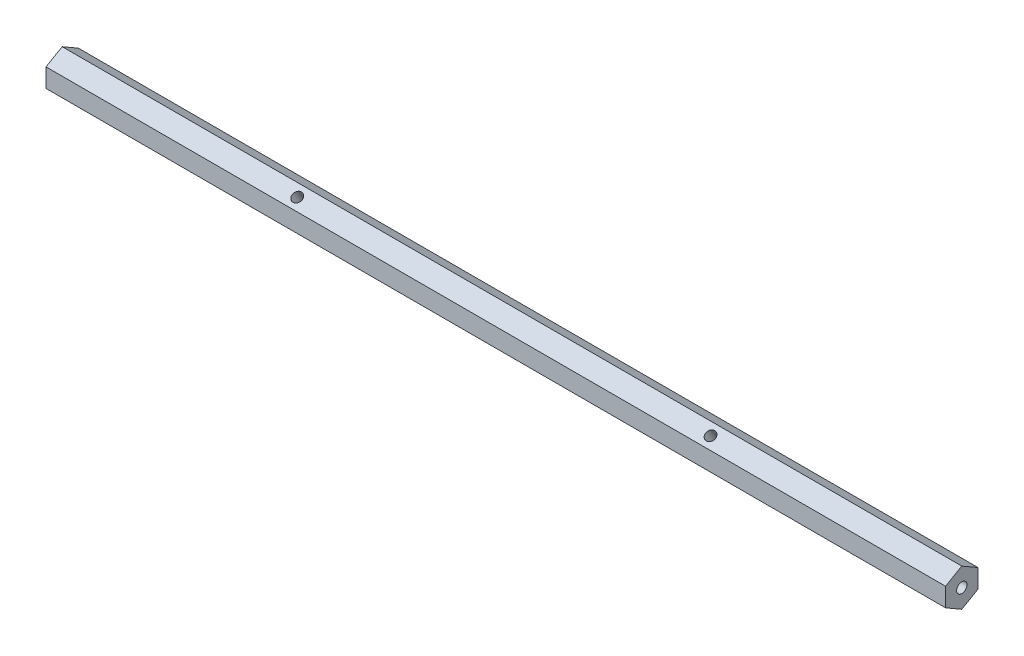
SolidWorks part; units mm, degrees
material "6061-T6 (SS)"
ref_plane "Front" through (0, 0, 0) normal (0, 0, 1) x (1, 0, 0)
ref_plane "Top" through (0, 0, 0) normal (0, 1, 0) x (1, 0, 0)
ref_plane "Right" through (0, 0, 0) normal (1, 0, 0) x (0, 0, -1)
ref_axis "Axis1" through (-80.9, 0, 0) along (1, 0, 0)
sketch "Sketch1" plane through (0, 0, 0) normal (1, 0, 0) x (0, 0, -1)
  line L1 (0, 7.3323) -> (-6.35, 3.6662)
  line L2 (-6.35, 3.6662) -> (-6.35, -3.6662)
  line L3 (-6.35, -3.6662) -> (0, -7.3323)
  line L4 (0, -7.3323) -> (6.35, -3.6662)
  line L5 (6.35, -3.6662) -> (6.35, 3.6662)
  line L6 (6.35, 3.6662) -> (0, 7.3323)
  circle A0 centre (0, 0) radius 6.35 construction
  dimension "D1" = 12.7
extrude "Boss-Extrude1" add sketch "Sketch1" along normal up to surface (352.425 mm away)
hole_wizard "#10-32 Tapped Hole1" positions "Sketch2" profile "Sketch3" tap size "#10-32" standard "ANSI Inch"
sketch "Sketch2" plane through (352.425, 0, 0) normal (1, 0, 0) x (0, 0, -1)
  point P0 (0, 0)
sketch "Sketch3" plane through (352.425, 0, 0) normal (0, 1, 0) x (0, 0, -1)
  line L0 (0, 0) -> (0, 13.2529)
  line L1 (0, 13.2529) -> (2.0193, 12.0396)
  line L2 (2.0193, 12.0396) -> (2.0193, 0)
  line L5 (2.0193, 0) -> (0, 0)
  line L10 (0, 13.2529) -> (-2.0193, 12.0396) construction
  line L11 (0, -6.35) -> (0, 107.95) construction
  dimension "Tap Drill Dia." = 4.0386
  dimension "Tap Drill Depth" = 12.0396
  dimension "Drill Angle" = 118
cosmetic thread "Hole Thread1" parameters "D1"=9.652, "D2"=4.826
hole_wizard "#10-32 Tapped Hole2" positions "Sketch4" profile "Sketch5" tap size "#10-32" standard "ANSI Inch"
sketch "Sketch4" plane through (0, 0, 0) normal (-1, 0, 0) x (0, 0, 1)
  point P0 (0, 0)
sketch "Sketch5" plane through (0, 0, 0) normal (0, 1, 0) x (0, 0, 1)
  line L0 (0, 0) -> (0, 13.2529)
  line L1 (0, 13.2529) -> (2.0193, 12.0396)
  line L2 (2.0193, 12.0396) -> (2.0193, 0)
  line L5 (2.0193, 0) -> (0, 0)
  line L10 (0, 13.2529) -> (-2.0193, 12.0396) construction
  line L11 (0, -6.35) -> (0, 107.95) construction
  dimension "Tap Drill Dia." = 4.0386
  dimension "Tap Drill Depth" = 12.0396
  dimension "Drill Angle" = 118
cosmetic thread "Hole Thread2" parameters "D1"=9.652, "D2"=4.826
sketch "Sketch6" plane through (0, 5.4993, 3.175) normal (0, 0.866, 0.5) x (1, 0, 0)
  line L0 (0, 7.3323) -> (0, 3.6662) construction
  line L3 (0, 0) -> (95.25, 0) construction
  line L4 (0, 3.6662) -> (0, -3.6662) construction
  line L9 (257.175, 0) -> (352.425, 0) construction
  line L10 (352.425, -3.6662) -> (352.425, 3.6662) construction
  circle A0 centre (95.25, 0) radius 1.905
  circle A1 centre (257.175, 0) radius 1.905
  dimension "D1" = 3.81
  dimension "D2" = 95.25
extrude "Cut-Extrude1" cut sketch "Sketch6" against normal through all
